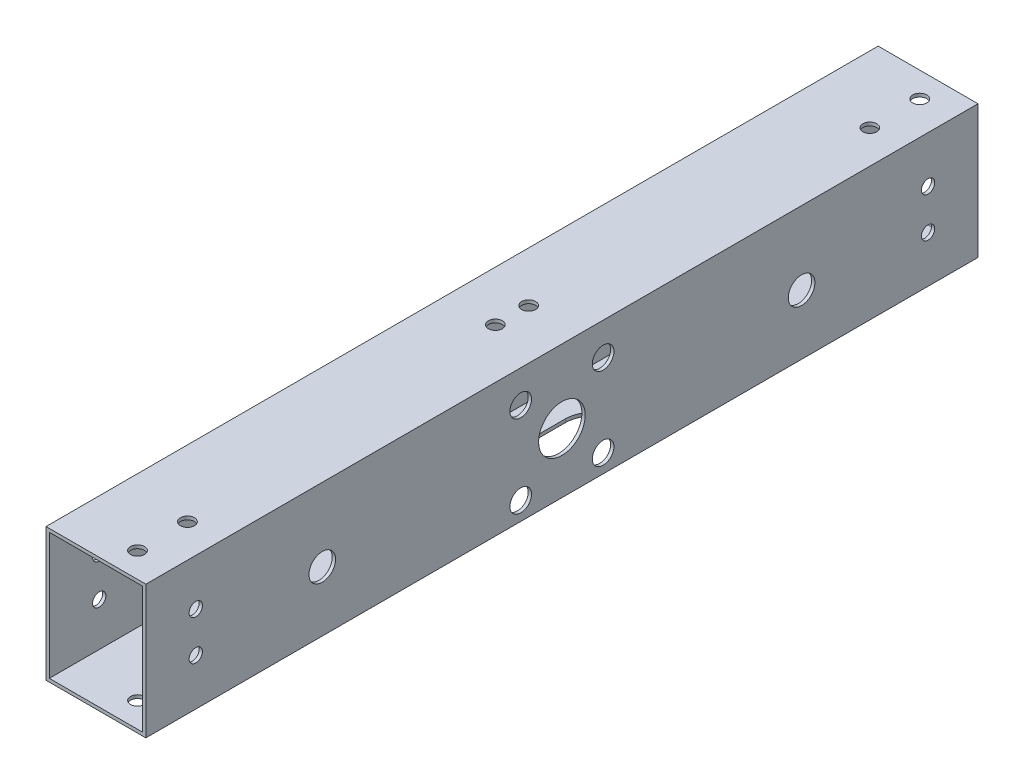
SolidWorks part; units mm, degrees
material "6061 合金"
ref_plane "前视基准面" through (0, 0, 0) normal (0, 0, 1) x (1, 0, 0)
ref_plane "上视基准面" through (0, 0, 0) normal (0, 1, 0) x (1, 0, 0)
ref_plane "右视基准面" through (0, 0, 0) normal (1, 0, 0) x (0, 0, -1)
other "Configuration Table"
sketch "草图1" plane through (0, 0, 0) normal (0, 0, 1) x (1, 0, 0)
  line L0 (15, -20) -> (15, 20)
  line L1 (15, 20) -> (-15, 20)
  line L2 (-15, 20) -> (-15, -20)
  line L3 (-15, -20) -> (15, -20)
  line L4 (14, 19) -> (-14, 19)
  line L5 (14, -19) -> (14, 19)
  line L6 (-14, -19) -> (14, -19)
  line L7 (-14, 19) -> (-14, -19)
extrude "凸台-拉伸1" add sketch "草图1" along normal blind 250
sketch "草图3" plane through (0, 20, 0) normal (0, 1, 0) x (1, 0, 0)
  line L0 (15, 0) -> (-15, 0) construction
  line L2 (-15, -125) -> (78.6025, -125) construction
  line L4 (-15, -250) -> (-15, 0) construction
  circle A0 centre (5, -7.5) radius 2.1
  circle A1 centre (5, -22.5) radius 2.1
  circle A4 centre (5, -227.5) radius 2.1
  circle A5 centre (5, -242.5) radius 2.1
  circle A6 centre (0, -120) radius 2.1
  circle A7 centre (0, -130) radius 2.1
  dimension "D1" = 4.2
  dimension "D2" = 7.5
  dimension "D4" = 20
  dimension "D5" = 4.2
  dimension "D6" = 10
  dimension "D3" = 2
extrude "切除-拉伸1" cut sketch "草图3" against normal blind 250
sketch "草图4" plane through (15, 0, 0) normal (1, 0, 0) x (0, 0, -1)
  line L0 (-250, 20) -> (0, 20) construction
  line L1 (0, -20) -> (0, 20) construction
  line L2 (-125, 20) -> (-125, -104.7599) construction
  circle A0 centre (-53, -2) radius 4
  circle A1 centre (-197, -2) radius 4
  dimension "D1" = 8
  dimension "D2" = 22
  dimension "D3" = 53
extrude "切除-拉伸2" cut sketch "草图4" against normal blind 250
sketch "草图5" plane through (-15, 0, 0) normal (-1, 0, 0) x (0, 0, 1)
  line L0 (250, 20) -> (0, 20) construction
  circle A0 centre (125, -2) radius 7
  dimension "D1" = 22
  dimension "D2" = 14
extrude "切除-拉伸3" cut sketch "草图5" against normal blind 250
sketch "草图6" plane through (0, -20, 0) normal (0, -1, 0) x (1, 0, 0)
  line L0 (-15, 250) -> (-15, 0) construction
  line L2 (-4, 145) -> (-4, 105)
  line L4 (13, 145) -> (13, 105)
  line L5 (-15, 125) -> (57.9688, 125) construction
  line L6 (15, 250) -> (15, 0) construction
  arc A0 (13, 145) -> (-4, 145) centre (4.5, 145) ccw
  arc A1 (-4, 105) -> (13, 105) centre (4.5, 105) ccw
  dimension "D4" = 20
  dimension "D5" = 8.5
  dimension "D7" = 10.5
  dimension "D8" = 8.5
  dimension "D2" = 11
  dimension "D1" = 17
  dimension "D3" = 40
  dimension "D6" = 2
extrude "切除-拉伸4" cut sketch "草图6" against normal blind 20
sketch "草图8" plane through (-15, 0, 0) normal (-1, 0, 0) x (0, 0, 1)
  line L0 (125, 20) -> (125, -55.4072) construction
  line L1 (250, 20) -> (0, 20) construction
  line L2 (250, -20) -> (0, -20) construction
  circle A0 centre (112.625, -14.5) radius 3.25
  circle A1 centre (137.375, -14.5) radius 3.25
  circle A2 centre (112.625, 10.25) radius 3.25
  circle A3 centre (137.375, 10.25) radius 3.25
  dimension "D1" = 24.75
  dimension "D2" = 5.5
  dimension "D4" = 24.75
  dimension "D5" = 6.5
  dimension "D3" = 2
extrude "切除-拉伸7" cut sketch "草图8" against normal blind 22 from offset 20 offset against normal yes
sketch "草图9" plane through (15, 0, 0) normal (1, 0, 0) x (0, 0, -1)
  line L1 (0, -20) -> (0, 20) construction
  line L2 (-15, 6) -> (-15, -6) construction
  line L3 (-125, 20) -> (-125, -94.4562) construction
  line L4 (-250, 20) -> (0, 20) construction
  line L5 (-235, 6) -> (-235, -6) construction
  line L6 (-250, -20) -> (0, -20) construction
  circle A0 centre (-15, 6) radius 2
  circle A1 centre (-15, -6) radius 2
  circle A2 centre (-235, -6) radius 2
  circle A3 centre (-235, 6) radius 2
  dimension "D1" = 4
  dimension "D2" = 4
  dimension "D3" = 14
  dimension "D4" = 12
  dimension "D5" = 15
extrude "切除-拉伸8" cut sketch "草图9" against normal blind 36
